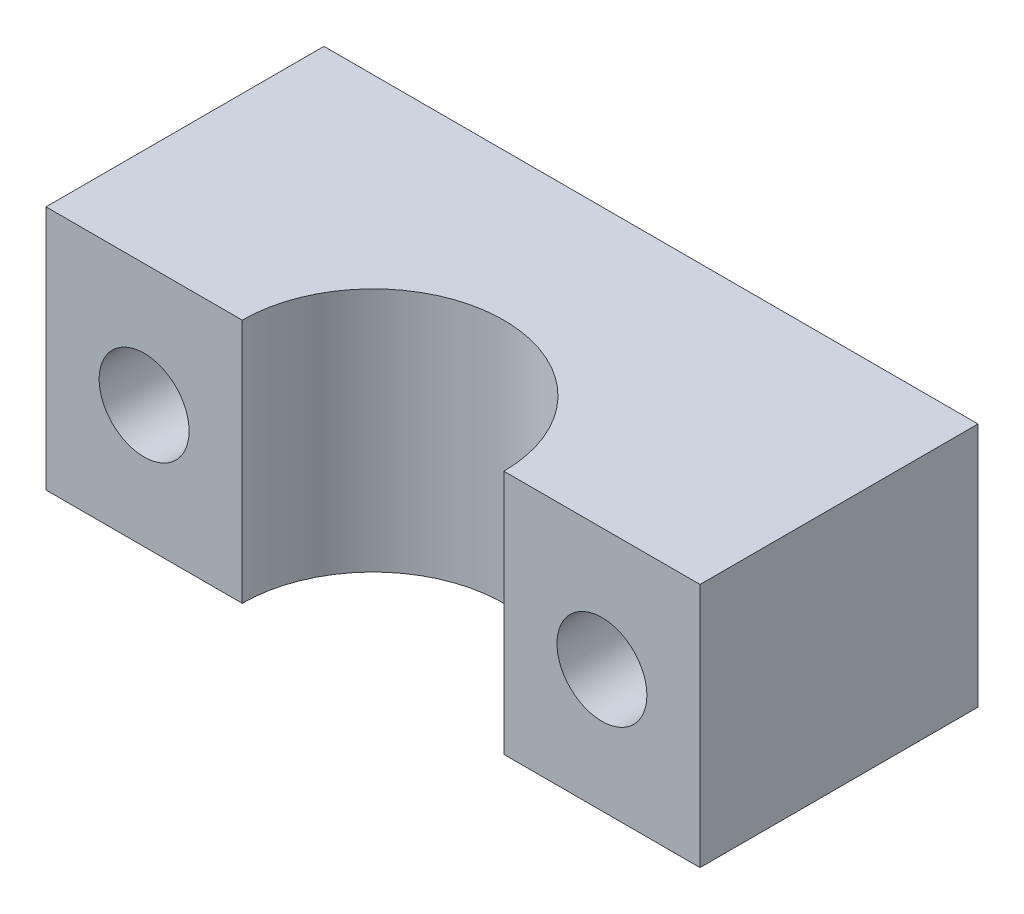
SolidWorks part; units mm, degrees
ref_plane "前视基准面" through (0, 0, 0) normal (0, 0, 1) x (1, 0, 0)
ref_plane "上视基准面" through (0, 0, 0) normal (0, 1, 0) x (1, 0, 0)
ref_plane "右视基准面" through (0, 0, 0) normal (1, 0, 0) x (0, 0, -1)
sketch "草图1" plane through (0, 0, 0) normal (0, 0, 1) x (1, 0, 0)
  line L1 (0, 0) -> (40, 0)
  line L2 (0, 0) -> (0, -15)
  line L3 (0, -15) -> (40, -15)
  line L4 (40, 0) -> (40, -15)
  dimension "D1" = 15
  dimension "D2" = 40
extrude "凸台-拉伸1" add sketch "草图1" along normal blind 17
sketch "草图2" plane through (0, 0, 0) normal (0, 1, 0) x (1, 0, 0)
  line L0 (40, -17) -> (0, -17) construction
  circle A0 centre (20, -17) radius 8
  dimension "D1" = 16
extrude "切除-拉伸1" cut sketch "草图2" against normal blind 15
sketch "草图4" plane through (0, 0, 17) normal (0, 0, 1) x (1, 0, 0)
  line L0 (12, 0) -> (0, 0) construction
  line L1 (40, 0) -> (28, 0) construction
  line L3 (28, 0) -> (12, 0) construction
  circle A0 centre (34, -7.5) radius 2.75
  circle A1 centre (6, -7.5) radius 2.75
  point P13 (20, 0)
  dimension "D1" = 5.5
  dimension "D2" = 5.5
  dimension "D3" = 28
  dimension "D4" = 7.5
  dimension "D5" = 7.5
  dimension "D6" = 14
extrude "切除-拉伸2" cut sketch "草图4" against normal through all
